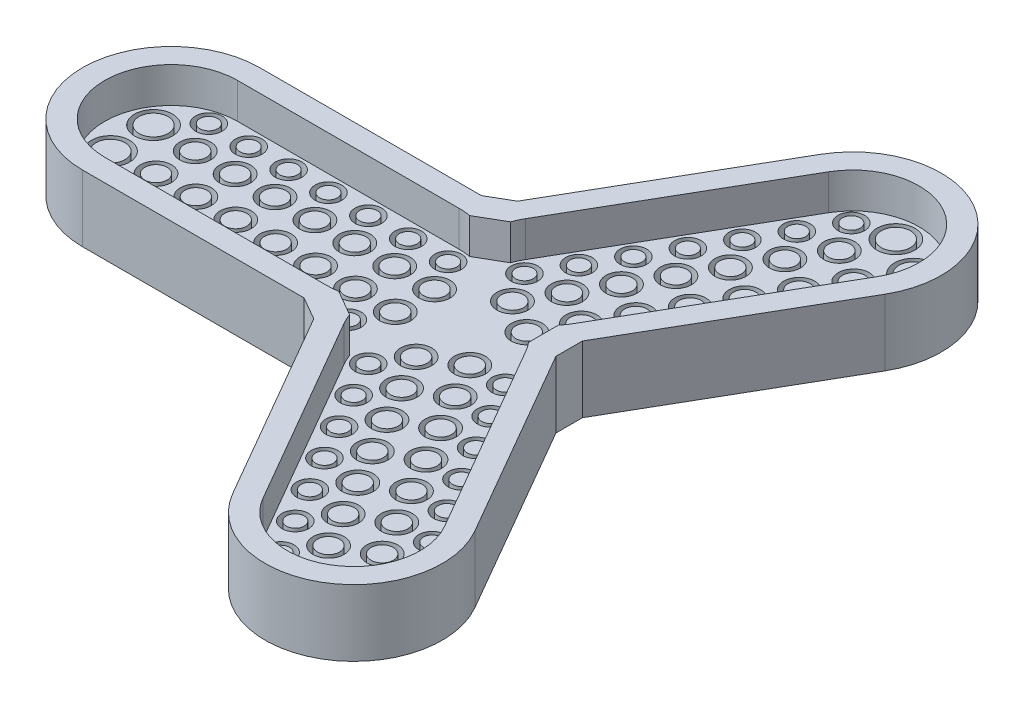
SolidWorks part; units mm, degrees
ref_plane "Front Plane" through (0, 0, 0) normal (0, 0, 1) x (1, 0, 0)
ref_plane "Top Plane" through (0, 0, 0) normal (0, 1, 0) x (1, 0, 0)
ref_plane "Right Plane" through (0, 0, 0) normal (1, 0, 0) x (0, 0, -1)
sketch "Sketch1" plane through (0, 0, 0) normal (0, 1, 0) x (1, 0, 0)
  line L0 (-25, 0) -> (25, 0) construction
  line L1 (-25, 15) -> (25, 15)
  line L2 (-25, -15) -> (25, -15)
  line L3 (-25, 20) -> (25, 20)
  line L4 (-25, -20) -> (25, -20)
  line L5 (89.8205, 46.2917) -> (64.8205, 2.9904)
  line L6 (55.1795, 66.2917) -> (30.1795, 22.9904)
  line L7 (72.5, 56.2917) -> (47.5, 12.9904) construction
  line L8 (85.4904, 48.7917) -> (60.4904, 5.4904)
  line L9 (59.5096, 63.7917) -> (34.5096, 20.4904)
  line L10 (55.1795, -66.2917) -> (30.1795, -22.9904)
  line L11 (89.8205, -46.2917) -> (64.8205, -2.9904)
  line L12 (72.5, -56.2917) -> (47.5, -12.9904) construction
  line L13 (59.5096, -63.7917) -> (34.5096, -20.4904)
  line L14 (85.4904, -48.7917) -> (60.4904, -5.4904)
  line L18 (25, 20) -> (30.1795, 22.9904)
  line L19 (27.5799, 14.7765) -> (33.4132, 18.1443)
  line L20 (27.5799, -14.7765) -> (33.4132, -18.1443)
  line L21 (25, -20) -> (30.1795, -22.9904)
  line L22 (64.8205, 2.9904) -> (64.8205, -2.9904)
  line L23 (59.0068, -3.3679) -> (59.0068, 3.3679)
  arc A0 (-25, 15) -> (-25, -15) centre (-25, 0) ccw
  arc A1 (25, -15) -> (27.5799, -14.7765) centre (25, 0) ccw
  arc A2 (25, -20) -> (33.4132, -18.1443) centre (25, 0) ccw
  arc A3 (-25, 20) -> (-25, -20) centre (-25, 0) ccw
  arc A4 (30.1795, 22.9904) -> (27.5799, 14.7765) centre (47.5, 12.9904) ccw
  arc A5 (89.8205, 46.2917) -> (55.1795, 66.2917) centre (72.5, 56.2917) ccw
  arc A6 (85.4904, 48.7917) -> (59.5096, 63.7917) centre (72.5, 56.2917) ccw
  arc A7 (34.5096, 20.4904) -> (33.4132, 18.1443) centre (47.5, 12.9904) ccw
  arc A8 (64.8205, -2.9904) -> (59.0068, 3.3679) centre (47.5, -12.9904) ccw
  arc A9 (55.1795, -66.2917) -> (89.8205, -46.2917) centre (72.5, -56.2917) ccw
  arc A10 (59.5096, -63.7917) -> (85.4904, -48.7917) centre (72.5, -56.2917) ccw
  arc A11 (60.4904, -5.4904) -> (59.0068, -3.3679) centre (47.5, -12.9904) ccw
  arc A16 (27.5799, 14.7765) -> (25, 15) centre (25, 0) ccw
  arc A17 (25, -15) -> (25, 15) centre (25, 0) ccw construction
  arc A18 (33.4132, 18.1443) -> (25, 20) centre (25, 0) ccw
  arc A19 (25, -20) -> (25, 20) centre (25, 0) ccw construction
  arc A20 (27.5799, -14.7765) -> (30.1795, -22.9904) centre (47.5, -12.9904) ccw
  arc A21 (33.4132, -18.1443) -> (34.5096, -20.4904) centre (47.5, -12.9904) ccw
  arc A23 (59.0068, 3.3679) -> (60.4904, 5.4904) centre (47.5, 12.9904) ccw
  arc A24 (59.0068, -3.3679) -> (64.8205, 2.9904) centre (47.5, 12.9904) ccw
  point P2 (0, 0)
  point P20 (60, 34.641)
  point P33 (60, -34.641)
  point P44 (40, 0)
  point P47 (60, 34.641)
  dimension "D2" = 30
  dimension "D3" = 5
  dimension "D4" = 3
extrude "Boss-Extrude1" add sketch "Sketch1" along normal blind 15 contours A20 A1 L2 A0 L1 A16 A4 A18 L3 A3 L4 A2 | A20 A2 L21 | L20 A20 A2 | A24 A11 L14 A10 L13 A21 A2 A20 L10 A9 L11 A8 | L23 A24 A8 | A24 A8 L22 | A8 A24 L5 A5 L6 A4 A18 A7 L9 A6 L8 A23 | L19 A18 A4 | A18 A4 L18 region at (-40.8381, 0, 0) region at (29.8543, 0, -17.5728) region at (31.38, 0, -20.002) region at (27.9307, 0, -20.9046) region at (29.8543, 0, 17.5728) region at (33.0094, 0, 19.7623) region at (27.9307, 0, 20.9046) region at (64.1385, 0, 0) region at (60.2913, 0, 0)
extrude "Boss-Extrude2" add sketch "Sketch1<2>" along normal blind 7 contours L2 A1 L1 A0 region at (40, 0, 0)
sketch "Sketch1<2>" plane through (0, 0, 0) normal (0, 1, 0) x (1, 0, 0) same geometry as "Sketch1"
sketch "Sketch2" plane through (0, 7, 0) normal (0, 1, 0) x (1, 0, 0)
  line L2 (-1000, 0) -> (49000, 0) construction
  line L3 (-25, -15) -> (25, -15)
  line L5 (-25, -15) -> (25, -15)
  line L16 (25, 15) -> (-25, 15)
  line L18 (25, 15) -> (-25, 15)
  line L20 (59.0068, -3.3679) -> (59.0068, 3.3679)
  line L22 (59.0068, -3.3679) -> (59.0068, 3.3679)
  line L24 (60.4904, 5.4904) -> (85.4904, 48.7917)
  line L26 (60.4904, 5.4904) -> (85.4904, 48.7917)
  line L28 (59.5096, 63.7917) -> (34.5096, 20.4904)
  line L30 (59.5096, 63.7917) -> (34.5096, 20.4904)
  line L31 (33.4132, 18.1443) -> (27.5799, 14.7765)
  line L32 (33.4132, 18.1443) -> (27.5799, 14.7765)
  line L33 (27.5799, -14.7765) -> (33.4132, -18.1443)
  line L34 (27.5799, -14.7765) -> (33.4132, -18.1443)
  line L35 (34.5096, -20.4904) -> (59.5096, -63.7917)
  line L36 (34.5096, -20.4904) -> (59.5096, -63.7917)
  line L37 (85.4904, -48.7917) -> (60.4904, -5.4904)
  line L38 (85.4904, -48.7917) -> (60.4904, -5.4904)
  circle A2 centre (-23.9882, 4.4317) radius 2.5
  circle A3 centre (-14.9882, 4.4317) radius 2.5
  arc A4 (25, -15) -> (27.5799, -14.7765) centre (25, 0) ccw
  circle A8 centre (-5.9882, 4.4317) radius 2.5
  circle A9 centre (3.0118, 4.4317) radius 2.5
  circle A10 centre (12.0118, 4.4317) radius 2.5
  circle A11 centre (21.0118, 4.4317) radius 2.5
  circle A12 centre (30.0118, 4.4317) radius 2.5
  circle A27 centre (30.0118, -4.4317) radius 2.5
  circle A28 centre (21.0118, -4.4317) radius 2.5
  circle A29 centre (12.0118, -4.4317) radius 2.5
  circle A30 centre (3.0118, -4.4317) radius 2.5
  circle A31 centre (-5.9882, -4.4317) radius 2.5
  circle A32 centre (-14.9882, -4.4317) radius 2.5
  circle A33 centre (-23.9882, -4.4317) radius 2.5
  circle A34 centre (-27.8096, -11.315) radius 2
  circle A35 centre (-18.8096, -11.315) radius 2
  circle A36 centre (-9.8096, -11.315) radius 2
  circle A37 centre (-0.8096, -11.315) radius 2
  circle A38 centre (8.1904, -11.315) radius 2
  circle A39 centre (17.1904, -11.315) radius 2
  circle A40 centre (26.1904, -11.315) radius 2
  circle A53 centre (26.1904, 11.315) radius 2
  circle A54 centre (17.1904, 11.315) radius 2
  circle A55 centre (8.1904, 11.315) radius 2
  circle A56 centre (-0.8096, 11.315) radius 2
  circle A57 centre (-9.8096, 11.315) radius 2
  circle A58 centre (-18.8096, 11.315) radius 2
  circle A59 centre (-27.8096, 11.315) radius 2
  circle A64 centre (30.0118, -4.4317) radius 3.5
  circle A65 centre (21.0118, -4.4317) radius 3.5
  circle A66 centre (12.0118, -4.4317) radius 3.5
  circle A67 centre (3.0118, -4.4317) radius 3.5
  circle A68 centre (-5.9882, -4.4317) radius 3.5
  circle A69 centre (-14.9882, -4.4317) radius 3.5
  circle A70 centre (-27.8096, -11.315) radius 3
  circle A71 centre (-18.8096, -11.315) radius 3
  circle A72 centre (-9.8096, -11.315) radius 3
  circle A73 centre (-0.8096, -11.315) radius 3
  circle A74 centre (8.1904, -11.315) radius 3
  circle A75 centre (17.1904, -11.315) radius 3
  circle A76 centre (26.1904, -11.315) radius 3
  circle A81 centre (-23.9882, -4.4317) radius 3.5
  circle A83 centre (-23.9882, 4.4317) radius 3.5
  circle A84 centre (-14.9882, 4.4317) radius 3.5
  circle A85 centre (-5.9882, 4.4317) radius 3.5
  circle A86 centre (3.0118, 4.4317) radius 3.5
  circle A87 centre (12.0118, 4.4317) radius 3.5
  circle A88 centre (21.0118, 4.4317) radius 3.5
  circle A89 centre (30.0118, 4.4317) radius 3.5
  circle A97 centre (26.1904, 11.315) radius 3
  circle A98 centre (17.1904, 11.315) radius 3
  circle A99 centre (8.1904, 11.315) radius 3
  circle A100 centre (-0.8096, 11.315) radius 3
  circle A101 centre (-9.8096, 11.315) radius 3
  circle A102 centre (-18.8096, 11.315) radius 3
  circle A103 centre (-27.8096, 11.315) radius 3
  circle A105 centre (-33.7648, 4.7998) radius 3.2873
  circle A106 centre (-33.5196, -5.1591) radius 3.2873
  circle A107 centre (-33.5196, -5.1591) radius 4.2873
  circle A108 centre (-33.7648, 4.7998) radius 4.2873
  circle A109 centre (75.8321, 53.1995) radius 2.5
  circle A110 centre (71.3321, 45.4053) radius 2.5
  arc A111 (25, -15) -> (27.5799, -14.7765) centre (25, 0) ccw
  circle A113 centre (66.8321, 37.6111) radius 2.5
  circle A114 centre (62.3321, 29.8169) radius 2.5
  circle A115 centre (57.8321, 22.0226) radius 2.5
  circle A116 centre (53.3321, 14.2284) radius 2.5
  circle A117 centre (48.8321, 6.4342) radius 2.5
  circle A118 centre (41.1561, 10.8659) radius 2.5
  circle A119 centre (45.6561, 18.6601) radius 2.5
  arc A120 (-25, 15) -> (-25, -15) centre (-25, 0) ccw
  arc A122 (-25, 15) -> (-25, -15) centre (-25, 0) ccw
  arc A124 (59.0068, 3.3679) -> (60.4904, 5.4904) centre (47.5, 12.9904) ccw
  arc A126 (59.0068, 3.3679) -> (60.4904, 5.4904) centre (47.5, 12.9904) ccw
  arc A128 (85.4904, 48.7917) -> (59.5096, 63.7917) centre (72.5, 56.2917) ccw
  arc A130 (85.4904, 48.7917) -> (59.5096, 63.7917) centre (72.5, 56.2917) ccw
  arc A132 (34.5096, 20.4904) -> (33.4132, 18.1443) centre (47.5, 12.9904) ccw
  arc A134 (34.5096, 20.4904) -> (33.4132, 18.1443) centre (47.5, 12.9904) ccw
  arc A135 (27.5799, 14.7765) -> (25, 15) centre (25, 0) ccw
  arc A136 (27.5799, 14.7765) -> (25, 15) centre (25, 0) ccw
  arc A137 (33.4132, -18.1443) -> (34.5096, -20.4904) centre (47.5, -12.9904) ccw
  arc A138 (33.4132, -18.1443) -> (34.5096, -20.4904) centre (47.5, -12.9904) ccw
  arc A139 (59.5096, -63.7917) -> (85.4904, -48.7917) centre (72.5, -56.2917) ccw
  arc A140 (59.5096, -63.7917) -> (85.4904, -48.7917) centre (72.5, -56.2917) ccw
  arc A141 (60.4904, -5.4904) -> (59.0068, -3.3679) centre (47.5, -12.9904) ccw
  arc A142 (60.4904, -5.4904) -> (59.0068, -3.3679) centre (47.5, -12.9904) ccw
  circle A143 centre (50.1561, 26.4544) radius 2.5
  circle A144 centre (54.6561, 34.2486) radius 2.5
  circle A145 centre (59.1561, 42.0428) radius 2.5
  circle A146 centre (63.6561, 49.837) radius 2.5
  circle A147 centre (68.1561, 57.6313) radius 2.5
  circle A148 centre (64.1057, 64.3824) radius 2
  circle A149 centre (59.6057, 56.5881) radius 2
  circle A150 centre (55.1057, 48.7939) radius 2
  circle A151 centre (50.6057, 40.9997) radius 2
  circle A152 centre (46.1057, 33.2054) radius 2
  circle A153 centre (41.6057, 25.4112) radius 2
  circle A154 centre (37.1057, 17.617) radius 2
  circle A155 centre (56.7039, 6.302) radius 2
  circle A156 centre (61.2039, 14.0962) radius 2
  circle A157 centre (65.7039, 21.8904) radius 2
  circle A158 centre (70.2039, 29.6847) radius 2
  circle A159 centre (74.7039, 37.4789) radius 2
  circle A160 centre (79.2039, 45.2731) radius 2
  circle A161 centre (83.7039, 53.0673) radius 2
  circle A162 centre (41.1561, 10.8659) radius 3.5
  circle A163 centre (45.6561, 18.6601) radius 3.5
  circle A164 centre (50.1561, 26.4544) radius 3.5
  circle A165 centre (54.6561, 34.2486) radius 3.5
  circle A166 centre (59.1561, 42.0428) radius 3.5
  circle A167 centre (63.6561, 49.837) radius 3.5
  circle A168 centre (64.1057, 64.3824) radius 3
  circle A169 centre (59.6057, 56.5881) radius 3
  circle A170 centre (55.1057, 48.7939) radius 3
  circle A171 centre (50.6057, 40.9997) radius 3
  circle A172 centre (46.1057, 33.2054) radius 3
  circle A173 centre (41.6057, 25.4112) radius 3
  circle A174 centre (37.1057, 17.617) radius 3
  circle A175 centre (68.1561, 57.6313) radius 3.5
  circle A176 centre (75.8321, 53.1995) radius 3.5
  circle A177 centre (71.3321, 45.4053) radius 3.5
  circle A178 centre (66.8321, 37.6111) radius 3.5
  circle A179 centre (62.3321, 29.8169) radius 3.5
  circle A180 centre (57.8321, 22.0226) radius 3.5
  circle A181 centre (53.3321, 14.2284) radius 3.5
  circle A182 centre (48.8321, 6.4342) radius 3.5
  circle A183 centre (56.7039, 6.302) radius 3
  circle A184 centre (61.2039, 14.0962) radius 3
  circle A185 centre (65.7039, 21.8904) radius 3
  circle A186 centre (70.2039, 29.6847) radius 3
  circle A187 centre (74.7039, 37.4789) radius 3
  circle A188 centre (79.2039, 45.2731) radius 3
  circle A189 centre (83.7039, 53.0673) radius 3
  circle A190 centre (81.0392, 61.4823) radius 3.2873
  circle A191 centre (72.2919, 66.2493) radius 3.2873
  circle A192 centre (72.2919, 66.2493) radius 4.2873
  circle A193 centre (81.0392, 61.4823) radius 4.2873
  circle A194 centre (68.1561, -57.6313) radius 2.5
  circle A195 centre (63.6561, -49.837) radius 2.5
  circle A196 centre (59.1561, -42.0428) radius 2.5
  circle A197 centre (54.6561, -34.2486) radius 2.5
  circle A198 centre (50.1561, -26.4544) radius 2.5
  circle A199 centre (45.6561, -18.6601) radius 2.5
  circle A200 centre (41.1561, -10.8659) radius 2.5
  circle A201 centre (48.8321, -6.4342) radius 2.5
  circle A202 centre (53.3321, -14.2284) radius 2.5
  circle A203 centre (57.8321, -22.0226) radius 2.5
  circle A204 centre (62.3321, -29.8169) radius 2.5
  circle A205 centre (66.8321, -37.6111) radius 2.5
  circle A206 centre (71.3321, -45.4053) radius 2.5
  circle A207 centre (75.8321, -53.1995) radius 2.5
  circle A208 centre (83.7039, -53.0673) radius 2
  circle A209 centre (79.2039, -45.2731) radius 2
  circle A210 centre (74.7039, -37.4789) radius 2
  circle A211 centre (70.2039, -29.6847) radius 2
  circle A212 centre (65.7039, -21.8904) radius 2
  circle A213 centre (61.2039, -14.0962) radius 2
  circle A214 centre (56.7039, -6.302) radius 2
  circle A215 centre (37.1057, -17.617) radius 2
  circle A216 centre (41.6057, -25.4112) radius 2
  circle A217 centre (46.1057, -33.2054) radius 2
  circle A218 centre (50.6057, -40.9997) radius 2
  circle A219 centre (55.1057, -48.7939) radius 2
  circle A220 centre (59.6057, -56.5881) radius 2
  circle A221 centre (64.1057, -64.3824) radius 2
  circle A222 centre (48.8321, -6.4342) radius 3.5
  circle A223 centre (53.3321, -14.2284) radius 3.5
  circle A224 centre (57.8321, -22.0226) radius 3.5
  circle A225 centre (62.3321, -29.8169) radius 3.5
  circle A226 centre (66.8321, -37.6111) radius 3.5
  circle A227 centre (71.3321, -45.4053) radius 3.5
  circle A228 centre (83.7039, -53.0673) radius 3
  circle A229 centre (79.2039, -45.2731) radius 3
  circle A230 centre (74.7039, -37.4789) radius 3
  circle A231 centre (70.2039, -29.6847) radius 3
  circle A232 centre (65.7039, -21.8904) radius 3
  circle A233 centre (61.2039, -14.0962) radius 3
  circle A234 centre (56.7039, -6.302) radius 3
  circle A235 centre (75.8321, -53.1995) radius 3.5
  circle A236 centre (68.1561, -57.6313) radius 3.5
  circle A237 centre (63.6561, -49.837) radius 3.5
  circle A238 centre (59.1561, -42.0428) radius 3.5
  circle A239 centre (54.6561, -34.2486) radius 3.5
  circle A240 centre (50.1561, -26.4544) radius 3.5
  circle A241 centre (45.6561, -18.6601) radius 3.5
  circle A242 centre (41.1561, -10.8659) radius 3.5
  circle A243 centre (37.1057, -17.617) radius 3
  circle A244 centre (41.6057, -25.4112) radius 3
  circle A245 centre (46.1057, -33.2054) radius 3
  circle A246 centre (50.6057, -40.9997) radius 3
  circle A247 centre (55.1057, -48.7939) radius 3
  circle A248 centre (59.6057, -56.5881) radius 3
  circle A249 centre (64.1057, -64.3824) radius 3
  circle A250 centre (72.7256, -66.2821) radius 3.2873
  circle A251 centre (81.2276, -61.0903) radius 3.2873
  circle A252 centre (81.2276, -61.0903) radius 4.2873
  circle A253 centre (72.7256, -66.2821) radius 4.2873
  point P387 (40, 0)
  dimension "D7" = 5
  dimension "D8" = 4
  dimension "D9" = 1
  dimension "D4" = 6
  dimension "D5" = 9
  dimension "D10" = 3
  dimension "D1" = 0
  dimension "D6" = 1
  dimension "D2" = 7
  dimension "D3" = 7
extrude "Cut-Extrude1" cut sketch "Sketch2" against normal blind 4 contours A107 A106 | A108 A105 | A83 A2 | A81 A33 | A69 A32 | A71 A35 | A70 A34 | A72 A36 | A84 A3 | A103 A59 | A102 A58 | A101 A57 | A100 A56 | A85 A8 | A86 A9 | A68 A31 | A67 A30 | A73 A37 | A74 A38 | A66 A29 | A87 A10 | A99 A55 | A98 A54 | A97 A53 | A89 A12 | A88 A11 | A65 A28 | A64 A27 | A76 A40 | A75 A39 | A243 A215 | A242 A200 | A241 A199 | A244 A216 | A240 A198 | A245 A217 | A223 A202 | A222 A201 | A234 A214 | A233 A213 | A224 A203 | A232 A212 | A225 A204 | A231 A211 | A239 A197 | A246 A218 | A238 A196 | A226 A205 | A247 A219 | A237 A195 | A227 A206 | A230 A210 | A248 A220 | A236 A194 | A249 A221 | A253 A250 | A252 A251 | A235 A207 | A228 A208 | A229 A209 | A168 A148 | A192 A191 | A193 A190 | A175 A147 | A169 A149 | A167 A146 | A176 A109 | A189 A161 | A177 A110 | A188 A160 | A170 A150 | A171 A151 | A166 A145 | A178 A113 | A187 A159 | A186 A158 | A179 A114 | A165 A144 | A172 A152 | A164 A143 | A180 A115 | A185 A157 | A173 A153 | A174 A154 | A162 A118 | A163 A119 | A181 A116 | A182 A117 | A183 A155 | A184 A156 region at (26.6108, 7, 4.4317) region at (17.6108, 7, 4.4317) region at (8.6108, 7, 4.4317) region at (-0.3892, 7, 4.4317) region at (-9.3892, 7, 4.4317) region at (-18.3892, 7, 4.4317) region at (-30.7248, 7, 11.315) region at (-21.7248, 7, 11.315) region at (-12.7248, 7, 11.315) region at (-3.7248, 7, 11.315) region at (5.2752, 7, 11.315) region at (14.2752, 7, 11.315) region at (23.2752, 7, 11.315) region at (-27.3892, 7, 4.4317) region at (-27.3892, 7, -4.4317) region at (-18.3892, 7, -4.4317) region at (-9.3892, 7, -4.4317) region at (-0.3892, 7, -4.4317) region at (8.6108, 7, -4.4317) region at (17.6108, 7, -4.4317) region at (26.6108, 7, -4.4317) region at (23.2752, 7, -11.315) region at (14.2752, 7, -11.315) region at (5.2752, 7, -11.315) region at (-3.7248, 7, -11.315) region at (-12.7248, 7, -11.315) region at (-21.7248, 7, -11.315) region at (-30.7248, 7, -11.315) region at (-37.6856, 7, 5.1591) region at (-37.9309, 7, -4.7998) region at (37.7551, 7, -10.8659) region at (42.2551, 7, -18.6601) region at (46.7551, 7, -26.4544) region at (51.2551, 7, -34.2486) region at (55.7551, 7, -42.0428) region at (60.2551, 7, -49.837) region at (61.1906, 7, -64.3824) region at (56.6906, 7, -56.5881) region at (52.1906, 7, -48.7939) region at (47.6906, 7, -40.9997) region at (43.1906, 7, -33.2054) region at (38.6906, 7, -25.4112) region at (34.1906, 7, -17.617) region at (64.7551, 7, -57.6313) region at (72.4311, 7, -53.1995) region at (67.9311, 7, -45.4053) region at (63.4311, 7, -37.6111) region at (58.9311, 7, -29.8169) region at (54.4311, 7, -22.0226) region at (49.9311, 7, -14.2284) region at (45.4311, 7, -6.4342) region at (53.7887, 7, -6.302) region at (58.2887, 7, -14.0962) region at (62.7887, 7, -21.8904) region at (67.2887, 7, -29.6847) region at (71.7887, 7, -37.4789) region at (76.2887, 7, -45.2731) region at (80.7887, 7, -53.0673) region at (68.1259, 7, -66.2493) region at (76.8732, 7, -61.4823)
